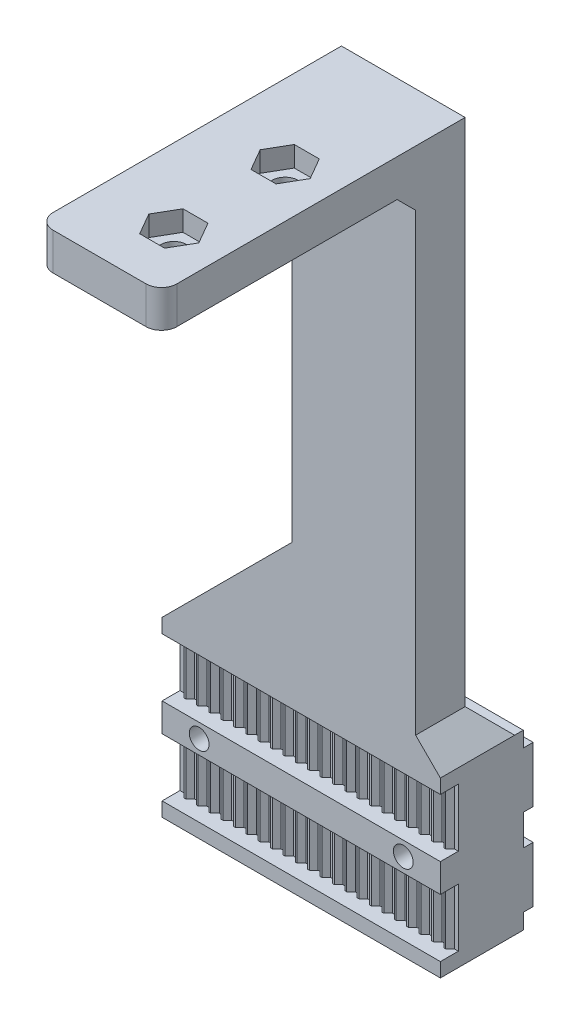
SolidWorks part; units mm, degrees
ref_plane "Спереди" through (0, 0, 0) normal (0, 0, 1) x (1, 0, 0)
ref_plane "Сверху" through (0, 0, 0) normal (0, 1, 0) x (1, 0, 0)
ref_plane "Справа" through (0, 0, 0) normal (1, 0, 0) x (0, 0, -1)
sketch "Эскиз1" plane through (0, 0, 0) normal (0, 0, 1) x (1, 0, 0)
  line L1 (0, -28) -> (-45, -28)
  line L2 (0, -28) -> (0, 0)
  line L3 (0, 0) -> (-45, 0)
  line L4 (-45, -28) -> (-45, 0)
  dimension "D1" = 28
  dimension "D2" = 45
extrude "Бобышка-Вытянуть1" add sketch "Эскиз1" along normal blind 13.4
sketch "Эскиз2" plane through (0, 0, 0) normal (0, 1, 0) x (1, 0, 0)
  line L6 (-45, 0) -> (-45, 1.6)
  line L90 (0, 0) -> (0, 1.6)
  line L91 (0, 0) -> (-45, 0)
  line L93 (-45, 1.6) -> (0, 1.6)
  dimension "D5" = 1.6
extrude "Бобышка-Вытянуть2" add sketch "Эскиз2" against normal blind 9 from offset 2.5 offset against normal yes
extrude "Бобышка-Вытянуть3" add sketch "Эскиз2<2>" against normal blind 9 from offset 16.5 offset against normal yes
sketch "Эскиз2<2>" plane through (0, 0, 0) normal (0, 1, 0) x (1, 0, 0) same geometry as "Эскиз2"
sketch "Эскиз3" plane through (0, 0, 13.4) normal (0, 0, 1) x (1, 0, 0)
  line L1 (-45, -2.3) -> (0, -2.3)
  line L2 (-45, -2.3) -> (-45, -11.7)
  line L3 (-45, -11.7) -> (0, -11.7)
  line L4 (0, -2.3) -> (0, -11.7)
  line L6 (-45, 0) -> (-45, -28) construction
  line L7 (0, -28) -> (0, 0) construction
  line L8 (0, 0) -> (-45, 0) construction
  line L9 (-45, -16.3) -> (0, -16.3)
  line L10 (-45, -16.3) -> (-45, -25.7)
  line L11 (-45, -25.7) -> (0, -25.7)
  line L12 (0, -16.3) -> (0, -25.7)
  line L13 (-45, -28) -> (0, -28) construction
  dimension "D1" = 9.4
  dimension "D2" = 45
  dimension "D3" = 9.4
  dimension "D4" = 45
  dimension "D5" = 4.6
  dimension "D6" = 2.3
  dimension "D7" = 2.3
extrude "Вырез-Вытянуть1" cut sketch "Эскиз3" against normal blind 2.9
sketch "Эскиз4" plane through (0, 0, 13.4) normal (0, 0, 1) x (1, 0, 0)
  line L0 (-45, -11.7) -> (-45, -16.3) construction
  line L1 (0, -16.3) -> (0, -11.7) construction
  circle A0 centre (-39, -14) radius 1.6
  circle A1 centre (-6, -14) radius 1.6
  point P9 (-45, -14)
  dimension "D1" = 3.2
  dimension "D2" = 3.2
  dimension "D4" = 6
  dimension "D3" = 6
extrude "Вырез-Вытянуть2" cut sketch "Эскиз4" against normal through all
sketch "Эскиз5" plane through (0, -2.3, 0) normal (0, -1, 0) x (1, 0, 0)
  line L0 (-45, 10.5) -> (-44.35, 10.5)
  line L1 (0, 10.5) -> (-45, 10.5) construction
  line L2 (-44.35, 10.5) -> (-43.65, 11.2)
  line L3 (-43.65, 11.2) -> (-43.35, 11.2)
  line L4 (-43.35, 11.2) -> (-42.65, 10.5)
  line L5 (-42.65, 10.5) -> (-42.35, 10.5)
  line L6 (-45, 10.5) -> (-45, 9.5)
  line L7 (-42.35, 10.5) -> (-41.65, 11.2)
  line L8 (-41.65, 11.2) -> (-41.35, 11.2)
  line L9 (-41.35, 11.2) -> (-40.65, 10.5)
  line L10 (-40.65, 10.5) -> (-40.35, 10.5)
  line L11 (-40.35, 10.5) -> (-39.65, 11.2)
  line L12 (-39.65, 11.2) -> (-39.35, 11.2)
  line L13 (-39.35, 11.2) -> (-38.65, 10.5)
  line L14 (-38.65, 10.5) -> (-38.35, 10.5)
  line L15 (-38.35, 10.5) -> (-37.65, 11.2)
  line L16 (-37.65, 11.2) -> (-37.35, 11.2)
  line L17 (-37.35, 11.2) -> (-36.65, 10.5)
  line L18 (-36.65, 10.5) -> (-36.35, 10.5)
  line L19 (-36.35, 10.5) -> (-35.65, 11.2)
  line L20 (-35.65, 11.2) -> (-35.35, 11.2)
  line L21 (-35.35, 11.2) -> (-34.65, 10.5)
  line L22 (-34.65, 10.5) -> (-34.35, 10.5)
  line L23 (-34.35, 10.5) -> (-33.65, 11.2)
  line L24 (-33.65, 11.2) -> (-33.35, 11.2)
  line L25 (-33.35, 11.2) -> (-32.65, 10.5)
  line L26 (-32.65, 10.5) -> (-32.35, 10.5)
  line L27 (-32.35, 10.5) -> (-31.65, 11.2)
  line L28 (-31.65, 11.2) -> (-31.35, 11.2)
  line L29 (-31.35, 11.2) -> (-30.65, 10.5)
  line L30 (-30.65, 10.5) -> (-30.35, 10.5)
  line L31 (-30.35, 10.5) -> (-29.65, 11.2)
  line L32 (-29.65, 11.2) -> (-29.35, 11.2)
  line L33 (-29.35, 11.2) -> (-28.65, 10.5)
  line L34 (-28.65, 10.5) -> (-28.35, 10.5)
  line L35 (-28.35, 10.5) -> (-27.65, 11.2)
  line L36 (-27.65, 11.2) -> (-27.35, 11.2)
  line L37 (-27.35, 11.2) -> (-26.65, 10.5)
  line L38 (-26.65, 10.5) -> (-26.35, 10.5)
  line L39 (-26.35, 10.5) -> (-25.65, 11.2)
  line L40 (-25.65, 11.2) -> (-25.35, 11.2)
  line L41 (-25.35, 11.2) -> (-24.65, 10.5)
  line L42 (-24.65, 10.5) -> (-24.35, 10.5)
  line L43 (-24.35, 10.5) -> (-23.65, 11.2)
  line L44 (-23.65, 11.2) -> (-23.35, 11.2)
  line L45 (-23.35, 11.2) -> (-22.65, 10.5)
  line L46 (-22.65, 10.5) -> (-22.35, 10.5)
  line L47 (-22.35, 10.5) -> (-21.65, 11.2)
  line L48 (-21.65, 11.2) -> (-21.35, 11.2)
  line L49 (-21.35, 11.2) -> (-20.65, 10.5)
  line L50 (-20.65, 10.5) -> (-20.35, 10.5)
  line L51 (-20.35, 10.5) -> (-19.65, 11.2)
  line L52 (-19.65, 11.2) -> (-19.35, 11.2)
  line L53 (-19.35, 11.2) -> (-18.65, 10.5)
  line L54 (-18.65, 10.5) -> (-18.35, 10.5)
  line L55 (-18.35, 10.5) -> (-17.65, 11.2)
  line L56 (-17.65, 11.2) -> (-17.35, 11.2)
  line L57 (-17.35, 11.2) -> (-16.65, 10.5)
  line L58 (-16.65, 10.5) -> (-16.35, 10.5)
  line L59 (-16.35, 10.5) -> (-15.65, 11.2)
  line L60 (-15.65, 11.2) -> (-15.35, 11.2)
  line L61 (-15.35, 11.2) -> (-14.65, 10.5)
  line L62 (-14.65, 10.5) -> (-14.35, 10.5)
  line L63 (-14.35, 10.5) -> (-13.65, 11.2)
  line L64 (-13.65, 11.2) -> (-13.35, 11.2)
  line L65 (-13.35, 11.2) -> (-12.65, 10.5)
  line L66 (-12.65, 10.5) -> (-12.35, 10.5)
  line L67 (-12.35, 10.5) -> (-11.65, 11.2)
  line L68 (-11.65, 11.2) -> (-11.35, 11.2)
  line L69 (-11.35, 11.2) -> (-10.65, 10.5)
  line L70 (-10.65, 10.5) -> (-10.35, 10.5)
  line L71 (-10.35, 10.5) -> (-9.65, 11.2)
  line L72 (-9.65, 11.2) -> (-9.35, 11.2)
  line L73 (-9.35, 11.2) -> (-8.65, 10.5)
  line L74 (-8.65, 10.5) -> (-8.35, 10.5)
  line L75 (-8.35, 10.5) -> (-7.65, 11.2)
  line L76 (-7.65, 11.2) -> (-7.35, 11.2)
  line L77 (-7.35, 11.2) -> (-6.65, 10.5)
  line L78 (-6.65, 10.5) -> (-6.35, 10.5)
  line L79 (-6.35, 10.5) -> (-5.65, 11.2)
  line L80 (-5.65, 11.2) -> (-5.35, 11.2)
  line L81 (-5.35, 11.2) -> (-4.65, 10.5)
  line L82 (-4.65, 10.5) -> (-4.35, 10.5)
  line L83 (-4.35, 10.5) -> (-3.65, 11.2)
  line L84 (-3.65, 11.2) -> (-3.35, 11.2)
  line L85 (-3.35, 11.2) -> (-2.65, 10.5)
  line L86 (-2.65, 10.5) -> (-2.35, 10.5)
  line L87 (-2.35, 10.5) -> (-1.65, 11.2)
  line L88 (-1.65, 11.2) -> (-1.35, 11.2)
  line L89 (-1.35, 11.2) -> (-0.65, 10.5)
  line L90 (-0.65, 10.5) -> (0, 10.5)
  line L91 (-45, 9.5) -> (0, 9.5)
  line L92 (0, 10.5) -> (0, 9.5)
  line L93 (-0.65, 10.5) -> (-0.35, 10.5) [skipped]
  dimension "D1" = 45
  dimension "D2" = 45
  dimension "D3" = 0.7
  dimension "D4" = 2
  dimension "D5" = 0.65
  dimension "D6" = 1
  dimension "D7" = 22
extrude "Бобышка-Вытянуть4" add sketch "Эскиз5" along normal up to surface (9.4 mm away) up to face at (-22.5, -11.7, 11.95)
extrude "Бобышка-Вытянуть5" add sketch "Эскиз5<2>" along normal up to surface (23.4 mm away) from surface up to face at (-22.5, -25.7, 11.95) starting at face at (-22.5, -16.3, 11.95)
sketch "Эскиз5<2>" plane through (0, -2.3, 0) normal (0, -1, 0) x (1, 0, 0) same geometry as "Эскиз5"
sketch "Эскиз17" plane through (0, -13.4, 13.4) normal (0, 0, -1) x (1, 0, 0)
  line L0 (0, -11.1) -> (0, -13.4) construction
  line L6 (-4, -13.4) -> (-45, -13.4)
  line L7 (-4, -13.4) -> (-4, -99.9)
  line L8 (-4, -99.9) -> (-24, -99.9)
  line L9 (-24, -34.4) -> (-24, -99.9)
  line L10 (-45, -13.4) -> (-24, -34.4)
  dimension "D1" = 20
  dimension "D2" = 86.5
  dimension "D3" = 4
  dimension "D4" = 45
extrude "Бобышка-Вытянуть16" add sketch "Эскиз17" along normal blind 8
sketch "Эскиз18" plane through (0, 86.5, 85.9) normal (0, -1, 0) x (1, 0, 0)
  line L1 (-4, -80.5) -> (-24, -80.5)
  line L2 (-4, -80.5) -> (-4, -31.4)
  line L3 (-4, -31.4) -> (-24, -31.4)
  line L4 (-24, -80.5) -> (-24, -31.4)
  line L7 (-24, -80.5) -> (-24, -72.5) construction
  line L10 (-24, -72.5) -> (-4, -72.5) construction
  dimension "D1" = 41.1
extrude "Бобышка-Вытянуть17" add sketch "Эскиз18" along normal blind 6
sketch "Эскиз19" plane through (0, 86.5, 0) normal (0, -1, 0) x (-1, 0, 0)
  line L0 (12, -26.5) -> (12, -44.5) construction
  line L1 (4, -54.5) -> (4, -13.4) construction
  line L2 (24, -54.5) -> (4, -54.5) construction
  circle A0 centre (12, -26.5) radius 2.1
  circle A1 centre (12, -44.5) radius 2.1
  dimension "D1" = 4.2
  dimension "D2" = 4.2
  dimension "D3" = 18
  dimension "D5" = 10
  dimension "D4" = 8
extrude "Вырез-Вытянуть5" cut sketch "Эскиз19" along normal through all
sketch "Эскиз20" plane through (0, 86.5, 0) normal (0, 1, 0) x (-1, 0, 0)
  line L1 (16.0415, 26.5) -> (14.0207, 30)
  line L2 (14.0207, 30) -> (9.9793, 30)
  line L3 (9.9793, 30) -> (7.9585, 26.5)
  line L4 (7.9585, 26.5) -> (9.9793, 23)
  line L5 (9.9793, 23) -> (14.0207, 23)
  line L6 (14.0207, 23) -> (16.0415, 26.5)
  line L7 (16.0415, 44.5) -> (14.0207, 48)
  line L8 (14.0207, 48) -> (9.9793, 48)
  line L9 (9.9793, 48) -> (7.9585, 44.5)
  line L10 (7.9585, 44.5) -> (9.9793, 41)
  line L11 (9.9793, 41) -> (14.0207, 41)
  line L12 (14.0207, 41) -> (16.0415, 44.5)
  circle A0 centre (12, 26.5) radius 3.5 construction
  circle A1 centre (12, 44.5) radius 3.5 construction
  dimension "D1" = 7
extrude "Вырез-Вытянуть6" cut sketch "Эскиз20" against normal blind 3.3
chamfer "Фаска1" distance 4 angle 45 2 edges at (-24.5, 0, 5.4) (-4, 0, 9.4)
chamfer "Фаска2" distance 3 angle 45 1 edges at (-14, 80.5, 13.4)
fillet "Скругление1" radius 2.5 2 edges at (-4, 83.5, 54.5) (-24, 83.5, 54.5)
